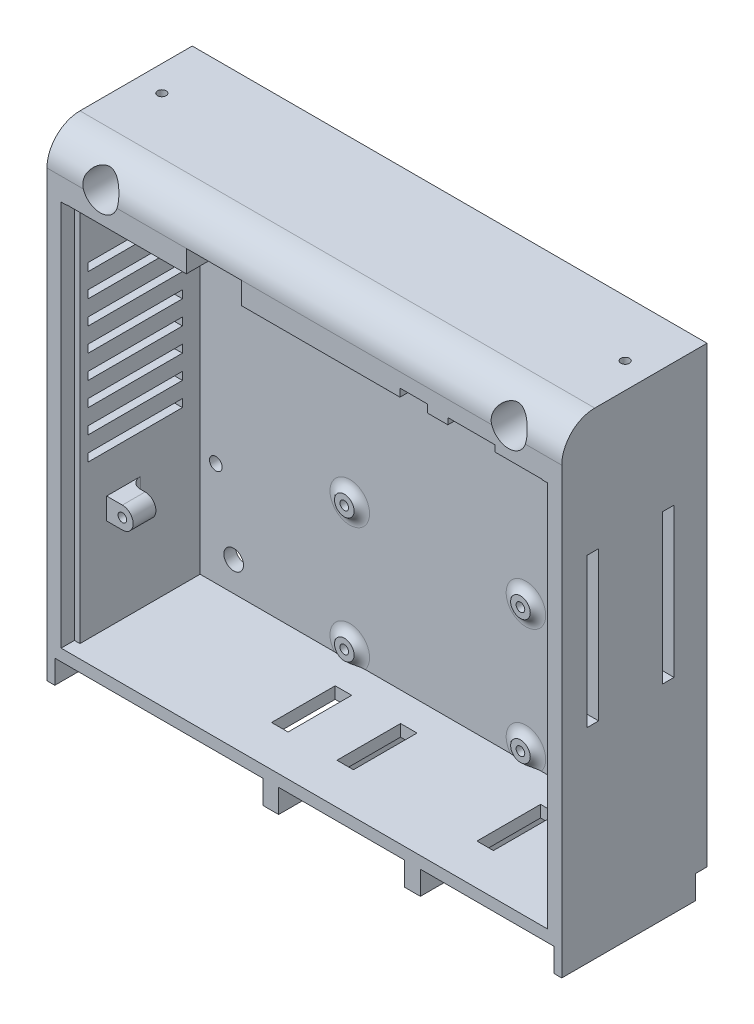
SolidWorks part; units mm, degrees
ref_plane "Alzado" through (0, 0, 0) normal (0, 0, 1) x (1, 0, 0)
ref_plane "Planta" through (0, 0, 0) normal (0, 1, 0) x (1, 0, 0)
ref_plane "Vista lateral" through (0, 0, 0) normal (1, 0, 0) x (0, 0, -1)
sketch "Croquis1" plane through (0, 0, 0) normal (0, 0, 1) x (1, 0, 0)
  line L1 (0, 0) -> (131.1, 0)
  line L2 (0, 0) -> (0, 109.5)
  line L3 (0, 109.5) -> (131.1, 109.5)
  line L4 (131.1, 0) -> (131.1, 109.5)
  dimension "D1" = 131.1
  dimension "D2" = 109.5
extrude "Saliente-Extruir2" add sketch "Croquis1" along normal blind 39
sketch "Croquis2" plane through (0, 0, 39) normal (0, 0, 1) x (1, 0, 0)
  line L0 (5, 101.5) -> (35.5, 101.5)
  line L1 (126.1, 101.5) -> (126.1, 3)
  line L2 (126.1, 3) -> (5, 3)
  line L3 (5, 3) -> (5, 101.5)
  line L4 (0, 109.5) -> (0, 0) construction
  line L5 (131.1, 0) -> (131.1, 109.5) construction
  line L6 (131.1, 109.5) -> (0, 109.5) construction
  line L7 (0, 0) -> (131.1, 0) construction
  line L8 (96.9, 101.5) -> (96.9, 103.5)
  line L9 (96.9, 103.5) -> (89.9, 103.5)
  line L10 (89.9, 103.5) -> (89.9, 101.5)
  line L11 (96.9, 101.5) -> (102.1, 101.5)
  line L12 (102.1, 101.5) -> (102.1, 103.1)
  line L13 (102.1, 103.1) -> (114.1, 103.1)
  line L14 (114.1, 103.1) -> (114.1, 101.5)
  line L15 (114.1, 101.5) -> (126.1, 101.5)
  line L17 (35.5, 101.5) -> (35.5, 107.1)
  line L18 (35.5, 107.1) -> (49.5, 107.1)
  line L19 (49.5, 107.1) -> (49.5, 101.5)
  line L20 (49.5, 101.5) -> (89.9, 101.5)
  point P20 (42.5, 101.5)
  point P24 (42.5, 101.5)
  dimension "D1" = 5
  dimension "D2" = 5
  dimension "D3" = 8
  dimension "D4" = 3
  dimension "D5" = 7
  dimension "D6" = 36.2
  dimension "D7" = 2
  dimension "D8" = 24
  dimension "D9" = 12
  dimension "D10" = 1.6
  dimension "D11" = 37.5
  dimension "D12" = 7
  dimension "D13" = 5.6
extrude "Cortar-Extruir1" cut sketch "Croquis2" against normal blind 36 contours L3 L0 L17 L18 L19 L20 L10 L9 L8 L11 L12 L13 L14 L15 L1 L2
ref_plane "Plano1" through (0, 0, 21) normal (0, 0, 1) x (1, 0, 0)
sketch "Croquis3" plane through (0, 0, 3) normal (0, 0, 1) x (1, 0, 0)
  line L0 (5, 101.5) -> (126.1, 101.5) construction
  line L1 (5, 101.5) -> (5, 3) construction
  line L2 (65.55, 101.5) -> (65.55, 3) construction
  line L3 (126.1, 3) -> (5, 3) construction
  line L5 (122.1, 26.65) -> (126.1, 26.65)
  line L6 (126.1, 101.5) -> (126.1, 3) construction
  line L7 (122.1, 32.15) -> (126.1, 32.15)
  line L8 (126.1, 101.5) -> (126.1, 3) construction
  line L9 (126.1, 32.15) -> (126.1, 26.65)
  line L10 (122.1, 94.75) -> (126.1, 94.75)
  line L11 (122.1, 100.25) -> (126.1, 100.25)
  line L12 (126.1, 100.25) -> (126.1, 94.75)
  line L13 (9, 100.25) -> (5, 100.25)
  line L14 (9, 94.75) -> (5, 94.75)
  line L15 (5, 94.75) -> (5, 100.25)
  line L16 (9, 26.65) -> (5, 26.65)
  line L17 (9, 32.15) -> (5, 32.15)
  line L18 (5, 32.15) -> (5, 26.65)
  circle A0 centre (9, 97.5) radius 2.75
  circle A1 centre (9, 97.5) radius 1.1
  circle A2 centre (122.1, 97.5) radius 2.75
  circle A3 centre (122.1, 97.5) radius 1.1
  circle A4 centre (9, 29.4) radius 2.75
  circle A5 centre (9, 29.4) radius 1.1
  circle A6 centre (122.1, 29.4) radius 2.75
  circle A7 centre (122.1, 29.4) radius 1.1
  point P16 (5, 25.4)
  line M10 (126.1, 3) -> (126.1, 101.5)
  line M20 (5, 101.5) -> (5, 3)
  dimension "D1" = 4
  dimension "D2" = 5.5
  dimension "D4" = 2.2
  dimension "D3" = 4
  dimension "D5" = 76.1
  dimension "D6" = 4
extrude "Saliente-Extruir6" add sketch "Croquis3" along normal blind 5.8 from surface contours A0 A1 | A0 L13 L14 M20 | A2 A3 | L11 A2 L10 M10 | A6 A7 | A6 L5 L7 M10 | A4 A5 | A4 L17 L16 M20 region at (125.0776, 29.4, 3) region at (125.0776, 97.5, 3) region at (119.4278, 29.4, 3) region at (119.4278, 97.5, 3) region at (6.0224, 97.5, 3) region at (6.0224, 29.4, 3) region at (10.8895, 99.3895, 3) region at (10.8895, 31.2895, 3) starting at plane "Plano1"
fillet "Redondeo1" radius 2.8 4 edges at (126.1, 97.5, 21) (126.1, 29.4, 21) (5, 97.5, 21) (5, 29.4, 21)
sketch "Croquis4" plane through (0, 0, 39) normal (0, 0, 1) x (1, 0, 0)
  line L0 (0, 109.5) -> (131.1, 109.5)
  line L1 (131.1, 109.5) -> (131.1, 115.5)
  line L2 (131.1, 115.5) -> (0, 115.5)
  line L3 (0, 115.5) -> (0, 109.5)
  dimension "D1" = 6
extrude "Saliente-Extruir7" add sketch "Croquis4" against normal up to vertex (39 mm away) contours L3 L0 L1 L2 up to point (0, 109.5, 0)
sketch "Croquis5" plane through (0, 0, 0) normal (-1, 0, 0) x (0, 0, 1)
  line L0 (19.5, 0) -> (19.5, 115.5) construction
  line L1 (39, 0) -> (0, 0) construction
  line L2 (0, 115.5) -> (39, 115.5) construction
  line L3 (7.5, 48) -> (7.5, 50)
  line L4 (7.5, 42) -> (31.5, 42)
  line L5 (7.5, 42) -> (7.5, 44)
  line L6 (7.5, 44) -> (31.5, 44)
  line L7 (31.5, 42) -> (31.5, 44)
  line L8 (7.5, 42) -> (31.5, 44) construction
  line L9 (7.5, 44) -> (31.5, 42) construction
  line L10 (7.5, 48) -> (31.5, 48)
  line L11 (31.5, 48) -> (31.5, 50)
  line L12 (7.5, 50) -> (31.5, 50)
  line L13 (7.5, 54) -> (7.5, 56)
  line L14 (7.5, 54) -> (31.5, 54)
  line L15 (31.5, 54) -> (31.5, 56)
  line L16 (7.5, 56) -> (31.5, 56)
  line L17 (7.5, 60) -> (7.5, 62)
  line L18 (7.5, 60) -> (31.5, 60)
  line L19 (31.5, 60) -> (31.5, 62)
  line L20 (7.5, 62) -> (31.5, 62)
  line L21 (7.5, 66) -> (7.5, 68)
  line L22 (7.5, 66) -> (31.5, 66)
  line L23 (31.5, 66) -> (31.5, 68)
  line L24 (7.5, 68) -> (31.5, 68)
  line L25 (7.5, 72) -> (7.5, 74)
  line L26 (7.5, 72) -> (31.5, 72)
  line L27 (31.5, 72) -> (31.5, 74)
  line L28 (7.5, 74) -> (31.5, 74)
  line L29 (7.5, 78) -> (7.5, 80)
  line L30 (7.5, 80) -> (31.5, 80)
  line L31 (31.5, 78) -> (31.5, 80)
  line L32 (7.5, 78) -> (31.5, 78)
  line L33 (7.5, 84) -> (7.5, 86)
  line L34 (7.5, 86) -> (31.5, 86)
  line L35 (31.5, 84) -> (31.5, 86)
  line L36 (7.5, 84) -> (31.5, 84)
  point P6 (19.5, 43)
  dimension "D1" = 24
  dimension "D2" = 2
  dimension "D3" = 42
  dimension "D4" = 6
  dimension "D5" = 3
extrude "Cortar-Extruir3" cut sketch "Croquis5" against normal up to next
sketch "Croquis6" plane through (131.1, 0, 0) normal (1, 0, 0) x (0, 0, -1)
  line L1 (-30.6, 46) -> (-27.6, 46)
  line L2 (-39, 0) -> (0, 0) construction
  line L3 (-30.6, 46) -> (-30.6, 84)
  line L4 (-30.6, 84) -> (-27.6, 84)
  line L5 (-27.6, 84) -> (-27.6, 46)
  line L6 (-19.5, 0) -> (-19.5, 115.5) construction
  line L7 (0, 115.5) -> (-39, 115.5) construction
  line L8 (-8.4, 84) -> (-11.4, 84)
  line L9 (-8.4, 46) -> (-8.4, 84)
  line L10 (-8.4, 46) -> (-11.4, 46)
  line L11 (-11.4, 84) -> (-11.4, 46)
  point P0 (-39, 115.5)
  dimension "D1" = 46
  dimension "D2" = 3
  dimension "D3" = 8.4
  dimension "D4" = 38
extrude "Cortar-Extruir4" cut sketch "Croquis6" against normal up to next
sketch "Croquis7" plane through (0, 0, 3) normal (0, 0, 1) x (1, 0, 0)
  circle A0 centre (122.1, 97.5) radius 1.1 construction
  circle A1 centre (122.1, 29.4) radius 1.1 construction
  circle A2 centre (9, 29.4) radius 1.1 construction
  circle A3 centre (9, 97.5) radius 1.1 construction
  circle A4 centre (122.1, 97.5) radius 1.1
  circle A5 centre (122.1, 29.4) radius 1.1
  circle A6 centre (9, 29.4) radius 1.1
  circle A7 centre (9, 97.5) radius 1.1
  circle A8 centre (9, 97.5) radius 1.6
  circle A9 centre (122.1, 97.5) radius 1.6
  circle A10 centre (122.1, 29.4) radius 1.6
  circle A11 centre (9, 29.4) radius 1.6
  dimension "D1" = 3.2
extrude "Cortar-Extruir5" cut sketch "Croquis7" against normal blind 10 contours A8 A7 | A7 | A4 | A9 A4 | A10 A5 | A5 | A6 | A11 A6 region at (122.1, 97.5, 3) region at (122.1, 29.4, 3) region at (9, 29.4, 3) region at (9, 97.5, 3) region at (7.4453, 97.5, 3) region at (120.5453, 97.5, 3) region at (120.5453, 29.4, 3) region at (7.4453, 29.4, 3)
sketch "Croquis9" plane through (0, 0, 39) normal (0, 0, 1) x (1, 0, 0)
  line L4 (0, 115.5) -> (0, 0)
  line L5 (0, 0) -> (131.1, 0)
  line L6 (131.1, 0) -> (131.1, 115.5)
  line L7 (131.1, 115.5) -> (0, 115.5)
  line L8 (0, 115.5) -> (0, 0)
  line L9 (0, 0) -> (131.1, 0)
  line L10 (131.1, 0) -> (131.1, 115.5)
  line L11 (131.1, 115.5) -> (0, 115.5)
  dimension "D1" = 0
extrude "Cortar-Extruir6" cut sketch "Croquis9" against normal blind 2
sketch "Croquis10" plane through (0, 0, 37) normal (0, 0, 1) x (1, 0, 0)
  line L0 (65.55, 0) -> (65.55, 115.5) construction
  line L1 (5, 3) -> (3.6, 3)
  line L2 (5, 3) -> (5, 101.3878)
  line L3 (5, 101.3878) -> (3.6, 101.3878)
  line L4 (3.6, 3) -> (3.6, 101.3878)
  line L5 (0, 0) -> (131.1, 0) construction
  line L6 (131.1, 115.5) -> (0, 115.5) construction
  line L7 (126.1, 101.3878) -> (127.5, 101.3878)
  line L8 (127.5, 3) -> (127.5, 101.3878)
  line L9 (126.1, 3) -> (127.5, 3)
  line L10 (126.1, 3) -> (126.1, 101.3878)
  dimension "D1" = 1.4
extrude "Cortar-Extruir7" cut sketch "Croquis10" against normal blind 3.4
sketch "Croquis12" plane through (0, 0, 37) normal (0, 0, 1) x (1, 0, 0)
  line L0 (65.55, 115.5) -> (65.55, 85.6878) construction
  line L1 (131.1, 115.5) -> (0, 115.5) construction
  line L2 (25.0028, 101.5) -> (25.0028, 115.5) construction
  line L3 (35.5, 101.5) -> (5, 101.5) construction
  circle A0 centre (13.55, 108.5) radius 4.5
  circle A1 centre (117.55, 108.5) radius 4.5
  circle A2 centre (13.55, 10.5) radius 4.5
  circle A3 centre (117.55, 10.5) radius 4.5
  point P6 (25.0028, 108.5)
  dimension "D1" = 9
  dimension "D2" = 52
  dimension "D3" = 2
sketch "Croquis13" plane through (0, 0, 37) normal (0, 0, 1) x (1, 0, 0)
  circle A0 centre (13.55, 108.5) radius 2.5
  circle A1 centre (117.55, 108.5) radius 2.5
  circle A2 centre (13.55, 10.5) radius 2.5
  circle A3 centre (117.55, 10.5) radius 2.5
  dimension "D1" = 5
extrude "Cortar-Extruir9" cut sketch "Croquis13" against normal up to next
extrude "Cortar-Extruir10" cut sketch "Croquis12" against normal blind 33
fillet "Redondeo3" radius 8.4 1 edges at (65.55, 115.5, 37)
sketch "Croquis14" plane through (0, 115.5, 0) normal (0, 1, 0) x (1, 0, 0)
  line L0 (65.55, 0) -> (65.55, -28.6) construction
  line L1 (131.1, 0) -> (0, 0) construction
  line L2 (0, -28.6) -> (131.1, -28.6) construction
  circle A0 centre (6.55, -14.3) radius 2.2
  circle A1 centre (124.55, -14.3) radius 2.2
  point P8 (0, 0)
  point P9 (65.55, -14.3)
  dimension "D1" = 4.4
  dimension "D2" = 59
sketch "Croquis15" plane through (0, 115.5, 0) normal (0, 1, 0) x (1, 0, 0)
  line L0 (65.55, 0) -> (65.55, -29.7725) construction
  line L1 (131.1, 0) -> (0, 0) construction
  circle A0 centre (6.55, -14.3) radius 1.1
  circle A1 centre (124.55, -14.3) radius 1.1
  dimension "D1" = 2.2
extrude "Cortar-Extruir11" cut sketch "Croquis15" against normal up to next
sketch "Croquis16" plane through (0, 0, 3) normal (0, 0, 1) x (1, 0, 0)
  line L0 (65.55, 0) -> (65.55, 42.1815) construction
  line L1 (0, 0) -> (131.1, 0) construction
  line L2 (39.95, 3) -> (91.15, 3)
  line L3 (126.1, 3) -> (5, 3) construction
  line L4 (91.15, 3) -> (91.15, 41.1)
  line L5 (91.15, 41.1) -> (39.95, 41.1)
  line L6 (39.95, 41.1) -> (39.95, 3)
  circle A0 centre (87.98, 6.17) radius 1.1
  circle A1 centre (43.12, 6.17) radius 1.1
  circle A2 centre (87.98, 37.93) radius 1.1
  circle A3 centre (43.12, 37.93) radius 1.1
  point P9 (65.55, 3)
  point P19 (65.55, 21.0907)
  dimension "D3" = 2.2
  dimension "D6" = 3.17
  dimension "D1" = 51.2
  dimension "D2" = 38.1
  dimension "D4" = 3.17
  dimension "D5" = 3.17
  dimension "D7" = 3.17
extrude "Cortar-Extruir13" cut sketch "Croquis16" against normal up to next contours A3 | A2 | A0 | A1 region at (87.98, 6.17, 3) region at (43.12, 6.17, 3) region at (87.98, 37.93, 3) region at (43.12, 37.93, 3)
sketch "Croquis17" plane through (0, 0, 3) normal (0, 0, 1) x (1, 0, 0)
  circle A0 centre (43.12, 6.17) radius 1.1 construction
  circle A1 centre (87.98, 6.17) radius 1.1 construction
  circle A2 centre (87.98, 37.93) radius 1.1 construction
  circle A3 centre (43.12, 37.93) radius 1.1 construction
  circle A4 centre (43.12, 6.17) radius 1.1
  circle A5 centre (87.98, 6.17) radius 1.1
  circle A6 centre (87.98, 37.93) radius 1.1
  circle A7 centre (43.12, 37.93) radius 1.1
  circle A8 centre (43.12, 37.93) radius 2.5
  circle A9 centre (87.98, 37.93) radius 2.5
  circle A10 centre (87.98, 6.17) radius 2.5
  circle A11 centre (43.12, 6.17) radius 2.5
  dimension "D1" = 5
extrude "Saliente-Extruir8" add sketch "Croquis17" along normal blind 1.4
fillet "Redondeo4" radius 3 4 edges at (85.48, 37.93, 3) (85.48, 6.17, 3) (40.62, 6.17, 3) (40.62, 37.93, 3)
sketch "Croquis18" plane through (0, 0, 0) normal (0, -1, 0) x (1, 0, 0)
  line L0 (0, 18.5) -> (131.1, 18.5) construction
  line L1 (0, 37) -> (0, 0) construction
  line L2 (131.1, 37) -> (131.1, 0) construction
  line L4 (63.45, 10.4) -> (67.65, 10.4)
  line L5 (63.45, 10.4) -> (63.45, 26.6)
  line L6 (63.45, 26.6) -> (67.65, 26.6)
  line L7 (67.65, 10.4) -> (67.65, 26.6)
  line L8 (63.45, 10.4) -> (67.65, 26.6) construction
  line L9 (63.45, 26.6) -> (67.65, 10.4) construction
  line L10 (46.8, 10.4) -> (51, 10.4)
  line L11 (46.8, 10.4) -> (46.8, 26.6)
  line L12 (46.8, 26.6) -> (51, 26.6)
  line L13 (51, 10.4) -> (51, 26.6)
  line L14 (46.8, 10.4) -> (51, 26.6) construction
  line L15 (46.8, 26.6) -> (51, 10.4) construction
  line L16 (99.1, 10.4) -> (103.3, 10.4)
  line L17 (99.1, 10.4) -> (99.1, 26.6)
  line L18 (99.1, 26.6) -> (103.3, 26.6)
  line L19 (103.3, 10.4) -> (103.3, 26.6)
  line L20 (99.1, 10.4) -> (103.3, 26.6) construction
  line L21 (99.1, 26.6) -> (103.3, 10.4) construction
  point P6 (65.55, 18.5)
  point P11 (57, 18.5)
  point P12 (93.1, 18.5)
  point P13 (48.9, 18.5)
  point P18 (101.2, 18.5)
  point P23 (0, 0)
  dimension "D1" = 4.2
  dimension "D2" = 16.2
  dimension "D3" = 57
  dimension "D4" = 38
  dimension "D5" = 4.2
  dimension "D6" = 16.2
  dimension "D7" = 6
  dimension "D8" = 4.2
  dimension "D9" = 6
extrude "Cortar-Extruir14" cut sketch "Croquis18" against normal up to next
sketch "Croquis19" plane through (0, 0, 37) normal (0, 0, 1) x (1, 0, 0)
  line L0 (0, 0) -> (57, 0)
  line L1 (0, 0) -> (131.1, 0) construction
  line L2 (57, 0) -> (57, -6)
  line L3 (57, -6) -> (55, -6)
  line L4 (55, -6) -> (55, 0)
  line L5 (0, 0) -> (0, -6)
  line L6 (0, -6) -> (2, -6)
  line L7 (2, -6) -> (2, 0)
  line L8 (131.1, 0) -> (93.1, 0)
  line L9 (93.1, 0) -> (93.1, -6)
  line L10 (93.1, -6) -> (95.1, -6)
  line L11 (95.1, -6) -> (95.1, 0)
  line L12 (131.1, 0) -> (131.1, -6)
  line L13 (131.1, -6) -> (129.1, -6)
  line L14 (129.1, -6) -> (129.1, 0)
  line L15 (57, -6) -> (59, -6)
  line L16 (59, -6) -> (59, 0)
  line L17 (59, 0) -> (91.1, 0)
  line L18 (91.1, 0) -> (91.1, -6)
  line L19 (91.1, -6) -> (93.1, -6)
  line M31 (0, 0) -> (131.1, 0)
  dimension "D1" = 57
  dimension "D2" = 2
  dimension "D3" = 6
  dimension "D4" = 38
  dimension "D5" = 2
  dimension "D6" = 2
extrude "Saliente-Extruir10" add sketch "Croquis19" against normal up to vertex (34 mm away) contours L6 L7 L5 M31 | L4 L3 L2 L0 | L15 L16 L2 M31 | L14 L13 L12 M31 | L10 L11 L9 M31 | L18 L19 L9 M31 region at (130.1, -3, 37) region at (92.1, -3, 37) region at (56, -3, 37) region at (1, -3, 37) region at (58, -3, 37) region at (94.1, -3, 37) up to point (84.0647, 3, 3)
